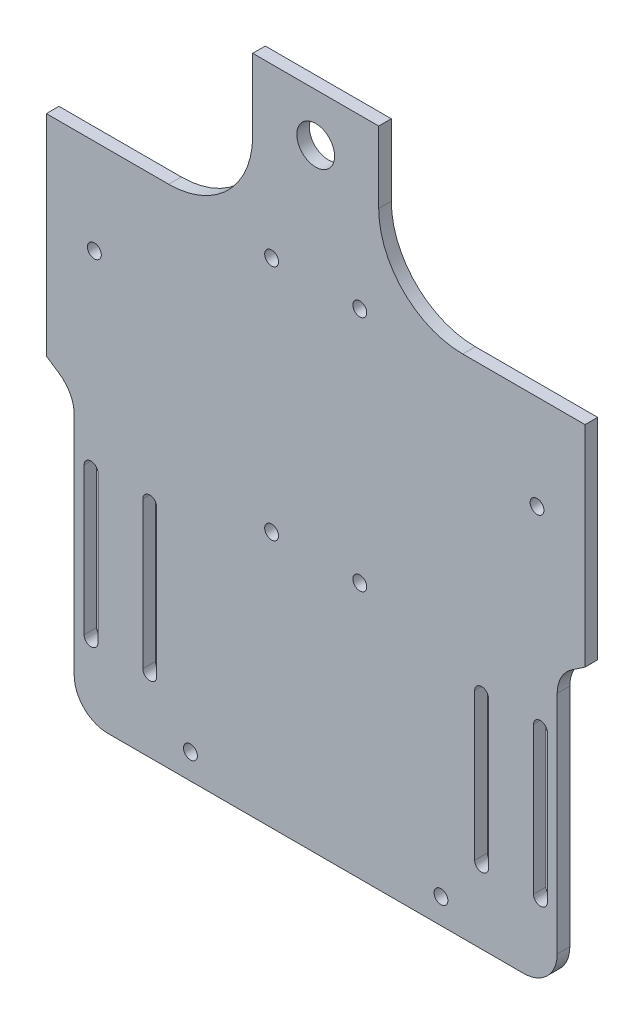
SolidWorks part; units mm, degrees
ref_plane "Front Plane" through (0, 0, 0) normal (0, 0, 1) x (1, 0, 0)
ref_plane "Top Plane" through (0, 0, 0) normal (0, 1, 0) x (1, 0, 0)
ref_plane "Right Plane" through (0, 0, 0) normal (1, 0, 0) x (0, 0, -1)
sketch "Sketch1" plane through (0, 0, 0) normal (0, 0, 1) x (1, 0, 0)
  line L0 (466.6281, 1797.6904) -> (466.6281, 1499.4405) construction
  line L7 (402.4958, 1683.2414) -> (402.4958, 1633.2414)
  line L8 (402.4958, 1633.2414) -> (409.1281, 1628.7679)
  line L9 (409.1281, 1628.7679) -> (409.1281, 1618.7679)
  line L14 (409.1281, 1562.7679) -> (524.1281, 1562.7679)
  line L18 (524.1281, 1628.7679) -> (524.1281, 1618.7679)
  line L20 (530.7604, 1633.2414) -> (524.1281, 1628.7679)
  line L21 (530.7604, 1683.2414) -> (530.7604, 1633.2414)
  line L25 (413.1281, 1615.2679) -> (413.1281, 1580.2679) construction
  line L26 (413.1281, 1615.2679) -> (413.1281, 1580.2679) construction
  line L27 (414.7781, 1615.2679) -> (414.7781, 1580.2679)
  line L28 (411.4781, 1615.2679) -> (411.4781, 1580.2679)
  line L30 (520.1281, 1615.2679) -> (520.1281, 1580.2679) construction
  line L31 (520.1281, 1615.2679) -> (520.1281, 1580.2679) construction
  line L32 (518.4781, 1615.2679) -> (518.4781, 1580.2679)
  line L33 (521.7781, 1615.2679) -> (521.7781, 1580.2679)
  line L35 (427.1281, 1615.2679) -> (427.1281, 1580.2679) construction
  line L36 (428.7781, 1615.2679) -> (428.7781, 1580.2679)
  line L37 (425.4781, 1615.2679) -> (425.4781, 1580.2679)
  line L38 (506.1281, 1615.2679) -> (506.1281, 1580.2679) construction
  line L39 (504.4781, 1615.2679) -> (504.4781, 1580.2679)
  line L40 (507.7781, 1615.2679) -> (507.7781, 1580.2679)
  line L41 (409.1281, 1618.7679) -> (409.1281, 1562.7679)
  line L42 (524.1281, 1618.7679) -> (524.1281, 1562.7679)
  line L49 (402.4958, 1683.2414) -> (451.6281, 1683.2414)
  line L53 (451.6281, 1683.2414) -> (451.6281, 1720.2414)
  line L54 (451.6281, 1720.2414) -> (481.6281, 1720.2414)
  line L55 (481.6281, 1683.2414) -> (481.6281, 1720.2414)
  line L56 (530.7604, 1683.2414) -> (481.6281, 1683.2414)
  line L57 (456.1281, 1681.137) -> (456.1281, 1666.6337) construction
  line L58 (448.6619, 1680.2858) -> (466.0117, 1680.2858) construction
  line L59 (456.1281, 1622.9345) -> (456.1281, 1637.4379) construction
  line L60 (448.6619, 1623.7858) -> (466.0117, 1623.7858) construction
  line L61 (484.5942, 1623.7858) -> (467.2444, 1623.7858) construction
  line L62 (477.1281, 1622.9345) -> (477.1281, 1637.4379) construction
  line L67 (477.1281, 1681.137) -> (477.1281, 1666.6337) construction
  line L68 (484.5942, 1680.2858) -> (467.2444, 1680.2858) construction
  line L70 (422.1949, 1708.7679) -> (505.4696, 1708.7679) construction
  line L71 (602.2349, 1683.2414) -> (337.9353, 1683.2414) construction
  line L72 (519.3209, 1708.8577) -> (519.3209, 1569.7658) construction
  line L73 (521.5101, 1660.6558) -> (543.6385, 1660.6558) construction
  line L86 (366.1855, 1652.0358) -> (561.5091, 1652.0358) construction
  line L101 (390.6897, 1568.7679) -> (530.1187, 1568.7679) construction
  line L114 (413.9353, 1708.8577) -> (413.9353, 1569.7658) construction
  line L115 (411.746, 1660.6558) -> (389.6176, 1660.6558) construction
  arc A0 (414.7781, 1615.2679) -> (411.4781, 1615.2679) centre (413.1281, 1615.2679) ccw
  arc A1 (411.4781, 1580.2679) -> (414.7781, 1580.2679) centre (413.1281, 1580.2679) ccw
  arc A2 (518.4781, 1615.2679) -> (521.7781, 1615.2679) centre (520.1281, 1615.2679) cw
  arc A3 (521.7781, 1580.2679) -> (518.4781, 1580.2679) centre (520.1281, 1580.2679) cw
  arc A4 (428.7781, 1615.2679) -> (425.4781, 1615.2679) centre (427.1281, 1615.2679) ccw
  arc A5 (425.4781, 1580.2679) -> (428.7781, 1580.2679) centre (427.1281, 1580.2679) ccw
  arc A6 (504.4781, 1615.2679) -> (507.7781, 1615.2679) centre (506.1281, 1615.2679) cw
  arc A7 (507.7781, 1580.2679) -> (504.4781, 1580.2679) centre (506.1281, 1580.2679) cw
  circle A12 centre (466.6281, 1708.7679) radius 4.5
  circle A13 centre (519.3209, 1660.6558) radius 1.65
  circle A20 centre (496.4498, 1568.7679) radius 1.65
  circle A24 centre (413.9353, 1660.6558) radius 1.65
  circle A26 centre (436.8064, 1568.7679) radius 1.65
  circle A27 centre (456.1281, 1680.2858) radius 1.65
  circle A28 centre (456.1281, 1623.7858) radius 1.65
  circle A29 centre (477.1281, 1623.7858) radius 1.65
  circle A30 centre (477.1281, 1680.2858) radius 1.65
  point P5 (466.6281, 1720.2414)
  point P17 (466.6281, 1562.7679)
  point P19 (520.1281, 1597.7679)
  point P29 (413.1281, 1597.7679)
  point P39 (427.1281, 1597.7679)
  point P46 (506.1281, 1597.7679)
  dimension "D17" = 28.25
  dimension "D12" = 3.3
  dimension "D20" = 29.8217
  dimension "D22" = 50
  dimension "D27" = 3.3
  dimension "D36" = 6
  dimension "D41" = 6
  dimension "D7" = 9
  dimension "D9" = 3.3
  dimension "D18" = 8
  dimension "D5" = 15
  dimension "D6" = 146
  dimension "D8" = 37
  dimension "D10" = 105.3856
  dimension "D11" = 115
  dimension "D13" = 14
  dimension "D14" = 3.3
  dimension "D15" = 4
  dimension "D16" = 10.5
  dimension "D19" = 21
  dimension "D21" = 29.8217
  dimension "D23" = 35
  dimension "D24" = 35
  dimension "D25" = 35
  dimension "D26" = 35
  dimension "D28" = 57.5
  dimension "D29" = 57.5
  dimension "D37" = 59.6434
extrude "Boss-Extrude1" add sketch "Sketch1" along normal blind 3
fillet "Fillet1" radius 8 4 edges at (524.1281, 1628.7679, 1.5) (409.1281, 1628.7679, 1.5) (409.1281, 1562.7679, 1.5) (524.1281, 1562.7679, 1.5)
fillet "Fillet3" radius 20 2 edges at (481.6281, 1683.2414, 1.5) (451.6281, 1683.2414, 1.5)
